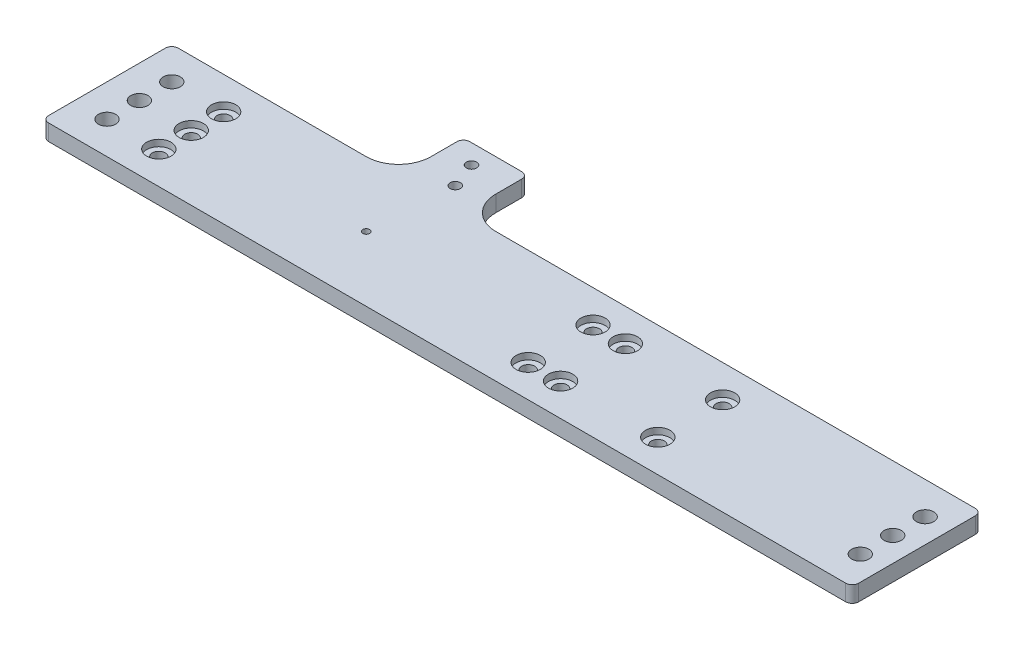
SolidWorks part; units mm, degrees
material "6061-T6 (SS)"
ref_plane "Front" through (0, 0, 0) normal (0, 0, 1) x (1, 0, 0)
ref_plane "Top" through (0, 0, 0) normal (0, 1, 0) x (1, 0, 0)
ref_plane "Right" through (0, 0, 0) normal (1, 0, 0) x (0, 0, -1)
sketch "Sketch1" plane through (0, 0, 0) normal (0, 1, 0) x (1, 0, 0)
  line L1 (-158.75, -25.4) -> (158.75, -25.4)
  line L2 (-158.75, -25.4) -> (-158.75, 25.4)
  line L3 (-158.75, 25.4) -> (158.75, 25.4)
  line L4 (158.75, -25.4) -> (158.75, 25.4)
  line L5 (-158.75, -25.4) -> (158.75, 25.4) construction
  line L6 (-158.75, 25.4) -> (158.75, -25.4) construction
  point P0 (0, 0)
  dimension "D1" = 50.8
  dimension "D2" = 317.5
extrude "Boss-Extrude1" add sketch "Sketch1" along normal blind 6.35
hole_wizard "CBORE for #10 Socket Head Cap Screw1" positions "Sketch2" profile "Sketch4" counterbore size "#10" standard "ANSI Inch" end condition through all
sketch "Sketch2" plane through (0, 6.35, 0) normal (0, 1, 0) x (1, 0, 0)
  line L2 (158.75, 25.4) -> (-158.75, 25.4) construction
  line L6 (-158.75, -25.4) -> (158.75, -25.4) construction
  line L8 (-158.75, 25.4) -> (-158.75, -25.4) construction
  line L12 (158.75, -25.4) -> (158.75, 25.4) construction
  line L15 (19.05, 12.7) -> (19.05, 25.4) construction
  line L17 (19.05, -12.7) -> (19.05, -25.4) construction
  line L18 (-125.73, -25.4) -> (-125.73, -12.7) construction
  line L20 (-125.73, 0) -> (-125.73, 12.7) construction
  line L21 (-125.73, 12.7) -> (-125.73, 25.4) construction
  line L22 (-125.73, 0) -> (-125.73, -12.7) construction
  point P64 (19.05, 12.7)
  point P66 (69.85, 12.7)
  point P68 (19.05, -12.7)
  point P70 (69.85, -12.7)
  point P92 (-125.73, 12.7)
  point P94 (-125.73, 0)
  point P102 (-125.73, -12.7)
  point P127 (31.75, 12.7)
  point P129 (31.75, -12.7)
  dimension "D1" = 38.1
  dimension "D2" = 50.8
  dimension "D3" = 25.4
  dimension "D4" = 88.9
  dimension "D5" = 33.02
sketch "Sketch4" plane through (31.75, 6.35, 12.7) normal (1, 0, 0) x (0, 0, 1)
  line L0 (0, 0) -> (0, 6.35)
  line L1 (0, 6.35) -> (2.5527, 6.35)
  line L3 (2.5527, 6.35) -> (2.5527, 2.54)
  line L4 (2.5527, 2.54) -> (4.7625, 2.54)
  line L5 (4.7625, 2.54) -> (4.7625, 0)
  line L7 (4.7625, 0) -> (0, 0)
  line L11 (0, -6.35) -> (0, 107.95) construction
  dimension "Thru Hole Dia." = 5.1054
  dimension "Thru Hole Depth" = 6.35
  dimension "C'Bore Dia." = 9.525
  dimension "C'Bore Depth" = 2.54
sketch "Sketch7" plane through (0, 0, 0) normal (0, -1, 0) x (1, 0, 0)
  line L0 (-146.05, 25.4) -> (-146.05, 12.7) construction
  line L1 (-158.75, 25.4) -> (158.75, 25.4) construction
  line L2 (-146.05, 12.7) -> (-146.05, 0) construction
  line L3 (-146.05, 0) -> (-146.05, -12.7) construction
  line L4 (-146.05, -12.7) -> (-146.05, -25.4) construction
  line L5 (158.75, -25.4) -> (-158.75, -25.4) construction
  line L7 (-158.75, -25.4) -> (-158.75, 25.4) construction
  line L8 (149.225, 25.4) -> (149.225, 12.7) construction
  line L9 (149.225, 12.7) -> (149.225, 0) construction
  line L10 (149.225, 0) -> (149.225, -12.7) construction
  line L11 (149.225, -12.7) -> (149.225, -25.4) construction
  line L13 (158.75, 25.4) -> (158.75, -25.4) construction
  point P0 (-146.05, 12.7)
  point P2 (-146.05, 0)
  point P4 (-146.05, -12.7)
  point P6 (149.225, 12.7)
  point P8 (149.225, 0)
  point P10 (149.225, -12.7)
  dimension "D1" = 12.7
  dimension "D2" = 9.525
hole_wizard "1/4 Clearance Hole2" positions "Sketch7" profile "Sketch6" hole size "1/4" standard "ANSI Inch" end condition through all
sketch "Sketch6" plane through (-146.05, 0, 12.7) normal (1, 0, 0) x (0, 0, -1)
  line L0 (0, 0) -> (0, 6.35)
  line L1 (0, 6.35) -> (3.3782, 6.35)
  line L2 (3.3782, 6.35) -> (3.3782, 0)
  line L5 (3.3782, 0) -> (0, 0)
  line L11 (0, -6.35) -> (0, 107.95) construction
  dimension "Thru Hole Dia." = 6.7564
  dimension "Thru Hole Depth" = 6.35
sketch "Sketch10" plane through (0, 0, 0) normal (0, -1, 0) x (-1, 0, 0)
  line L0 (158.75, 25.4) -> (158.75, -25.4) construction
  point P0 (57.15, 0)
  dimension "D1" = 101.6
hole_wizard "#6-32 Tapped Hole1" positions "Sketch10" profile "Sketch9" tap size "#6-32" standard "ANSI Inch" end condition through all
sketch "Sketch9" plane through (-57.15, 0, 0) normal (1, 0, 0) x (0, 0, -1)
  line L0 (0, 0) -> (0, 6.35)
  line L1 (0, 6.35) -> (1.3525, 6.35)
  line L2 (1.3525, 6.35) -> (1.3525, 0)
  line L5 (1.3525, 0) -> (0, 0)
  line L11 (0, -6.35) -> (0, 107.95) construction
  dimension "Thru Tap Drill Dia." = 2.7051
  dimension "Thru Tap Drill Depth" = 6.35
cosmetic thread "Hole Thread1" parameters "D2"=3.5052
sketch "Sketch11" plane through (0, 0, 0) normal (0, -1, 0) x (1, 0, 0)
  line L0 (158.75, -25.4) -> (-158.75, -25.4) construction
  line L1 (-70.0118, -25.4) -> (-48.1024, -25.4)
  line L2 (-70.0118, -25.4) -> (-70.0118, -45.81)
  line L3 (-70.0118, -45.81) -> (-48.1024, -45.81)
  line L4 (-48.1024, -25.4) -> (-48.1024, -45.81)
extrude "Boss-Extrude2" [suppressed] add sketch "Sketch11" against normal up to surface (6.35 mm away) up to face at (-57.15, 6.35, -1.3526)
sketch "Sketch12" plane through (0, 6.35, 0) normal (0, 1, 0) x (1, 0, 0)
  line L5 (-158.75, 25.4) -> (-158.75, -25.4) construction
  line L6 (-69.85, 25.4) -> (-69.85, 50.8)
  line L7 (158.75, 25.4) -> (-158.75, 25.4) construction
  line L8 (-69.85, 50.8) -> (-44.45, 50.8)
  line L9 (-44.45, 50.8) -> (-44.45, 25.4)
  line L10 (-69.85, 25.4) -> (-44.45, 25.4)
  dimension "D4" = 88.9
  dimension "D5" = 25.4
  dimension "D6" = 25.4
extrude "Boss-Extrude3" add sketch "Sketch12" against normal up to surface (6.35 mm away) up to face at (-57.15, 0, -1.3526)
sketch "Sketch15" plane through (0, 0, 0) normal (0, -1, 0) x (-1, 0, 0)
  point P0 (59.055, 43.18)
  point P3 (55.245, 33.02)
hole_wizard "#10-32 Tapped Hole1" positions "Sketch15" profile "Sketch14" tap size "#10-32" standard "ANSI Inch" end condition through all
sketch "Sketch14" plane through (-59.055, 0, -43.18) normal (1, 0, 0) x (0, 0, -1)
  line L0 (0, 0) -> (0, 6.35)
  line L1 (0, 6.35) -> (2.0193, 6.35)
  line L2 (2.0193, 6.35) -> (2.0193, 0)
  line L5 (2.0193, 0) -> (0, 0)
  line L11 (0, -6.35) -> (0, 107.95) construction
  dimension "Thru Tap Drill Dia." = 4.0386
  dimension "Thru Tap Drill Depth" = 6.35
fillet "Fillet1" radius 12.7 2 edges at (-44.45, 3.175, -25.4) (-69.85, 3.175, -25.4)
fillet "Fillet2" radius 2.54 6 edges at (158.75, 3.175, -25.4) (158.75, 3.175, 25.4) (-158.75, 3.175, 25.4) (-158.75, 3.175, -25.4) (-69.85, 3.175, -50.8) (-44.45, 3.175, -50.8)
